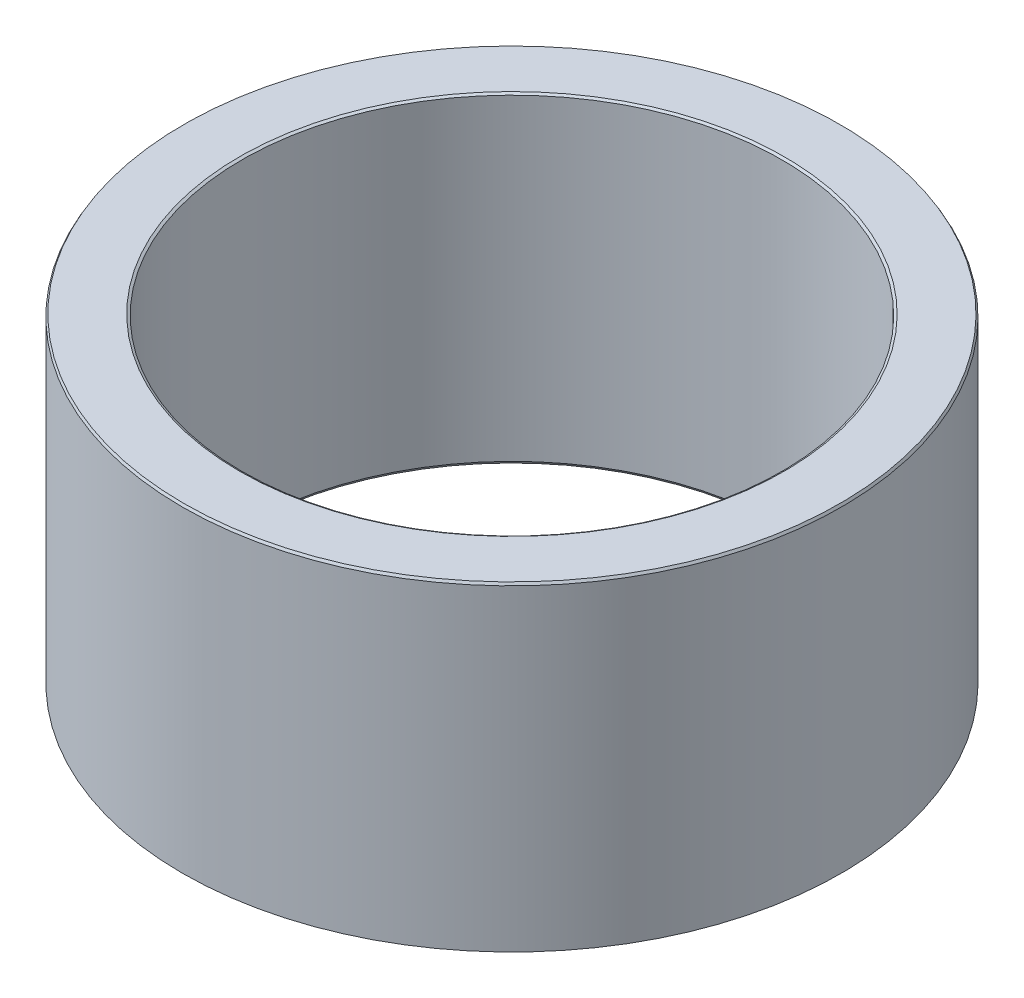
SolidWorks part; units mm, degrees
ref_plane "Front Plane" through (0, 0, 0) normal (0, 0, 1) x (1, 0, 0)
ref_plane "Top Plane" through (0, 0, 0) normal (0, 1, 0) x (1, 0, 0)
ref_plane "Right Plane" through (0, 0, 0) normal (1, 0, 0) x (0, 0, -1)
sketch "Sketch1" plane through (0, 0, 0) normal (0, 1, 0) x (1, 0, 0)
  circle A0 centre (0, 0) radius 30
  dimension "SLEEVE_OD" = 60
extrude "Boss-Extrude1" add sketch "Sketch1" along normal blind 29.2173
sketch "Sketch2" plane through (0, 0, 0) normal (0, 1, 0) x (1, 0, 0)
  circle A0 centre (0, 0) radius 24.5747
  dimension "BORE_D" = 49.1493
extrude "Cut-Extrude1" cut sketch "Sketch2" along normal through all
chamfer "Chamfer1" distance 0.2212 angle 30 4 edges at (0, 29.2173, 24.5747) (0, 0, 24.5747) (0, 0, 30) (0, 29.2173, 30) first distance on face at (0, 29.2173, 24.5747) first distance on face at (0, 0, 24.5747) first distance on face at (0, 29.2173, 30)
